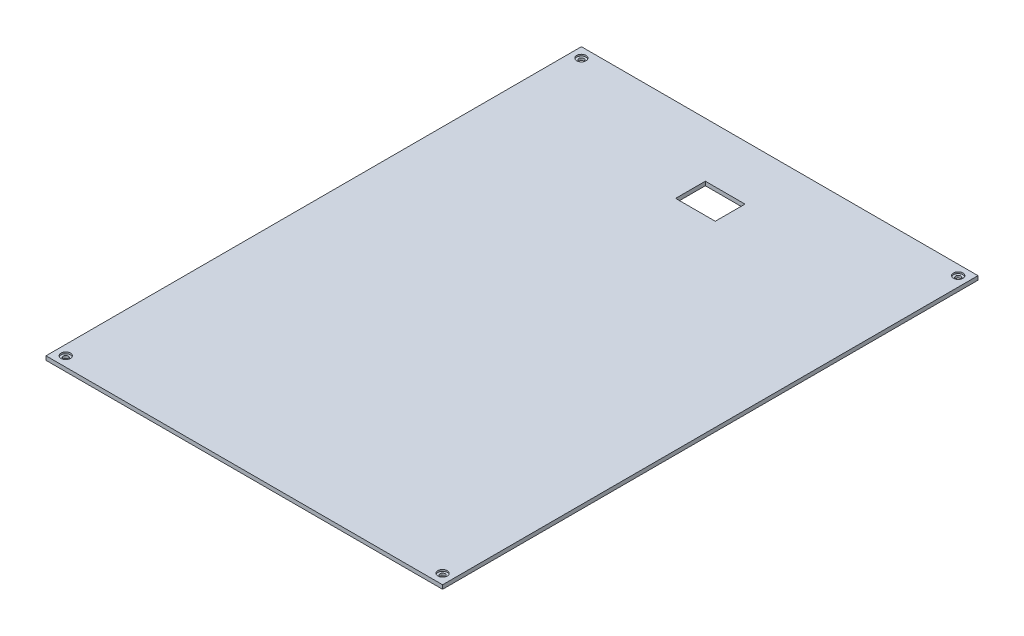
SolidWorks part; units mm, degrees
material "PLA"
ref_plane "Спереди" through (0, 0, 0) normal (0, 0, 1) x (1, 0, 0)
ref_plane "Сверху" through (0, 0, 0) normal (0, 1, 0) x (1, 0, 0)
ref_plane "Справа" through (0, 0, 0) normal (1, 0, 0) x (0, 0, -1)
sketch "Эскиз1" plane through (0, 0, 0) normal (0, 1, 0) x (1, 0, 0)
  line L1 (100, 135) -> (-100, 135)
  line L2 (100, 135) -> (100, -135)
  line L3 (100, -135) -> (-100, -135)
  line L4 (-100, 135) -> (-100, -135)
  line L5 (100, 135) -> (-100, -135) construction
  line L6 (100, -135) -> (-100, 135) construction
  point P0 (0, 0)
  dimension "D1" = 200
  dimension "D2" = 270
extrude "Бобышка-Вытянуть1" add sketch "Эскиз1" along normal blind 2
sketch "Эскиз2" plane through (0, 2, 0) normal (0, 1, 0) x (1, 0, 0)
  line L0 (0, 0) -> (0, 50000) construction
  line L1 (0, 0) -> (-50000, 0) construction
  line L2 (-100, 135) -> (-100, -135) construction
  line L3 (100, 135) -> (-100, 135) construction
  circle A0 centre (-95.0102, 130.0102) radius 1.3
  circle A1 centre (95.0102, 130.0102) radius 1.3
  circle A2 centre (95.0102, -130.0102) radius 1.3
  circle A3 centre (-95.0102, -130.0102) radius 1.3
  dimension "D1" = 2.6
  dimension "D2" = 4.9898
  dimension "D3" = 4.9898
extrude "Вырез-Вытянуть1" cut sketch "Эскиз2" against normal through all
sketch "Эскиз3" plane through (0, 2, 0) normal (0, 1, 0) x (1, 0, 0)
  circle A0 centre (-95.0102, 130.0102) radius 2.375
  circle A1 centre (95.0102, 130.0102) radius 2.375
  circle A2 centre (-95.0102, -130.0102) radius 2.375
  circle A3 centre (95.0102, -130.0102) radius 2.375
  dimension "D1" = 4.75
extrude "Вырез-Вытянуть2" cut sketch "Эскиз3" against normal blind 0.8
sketch "Эскиз4" plane through (0, 2, 0) normal (0, 1, 0) x (1, 0, 0)
  line L0 (0, 0) -> (0, 50000) construction
  line L1 (10, 107.5) -> (-10, 107.5)
  line L2 (10, 107.5) -> (10, 92.5)
  line L3 (10, 92.5) -> (-10, 92.5)
  line L4 (-10, 107.5) -> (-10, 92.5)
  line L5 (10, 107.5) -> (-10, 92.5) construction
  line L6 (10, 92.5) -> (-10, 107.5) construction
  line L7 (100, 135) -> (-100, 135) construction
  point P0 (0, 100)
  point P8 (0, 99.7252)
  dimension "D1" = 20
  dimension "D2" = 15
  dimension "D3" = 35
extrude "Вырез-Вытянуть3" cut sketch "Эскиз4" against normal through all
sketch "Эскиз5" plane through (0, 0, 0) normal (0, -1, 0) x (1, 0, 0)
  line L0 (100, -135) -> (-100, -135) construction
  line L1 (100, 135) -> (100, -135) construction
  circle A0 centre (-3.9, -120.15) radius 1.75
  circle A1 centre (6.25, -88.45) radius 1.75
  circle A2 centre (-3.9, -120.15) radius 2.75
  circle A3 centre (6.25, -88.45) radius 2.75
  dimension "D1" = 3.5
  dimension "D2" = 14.85
  dimension "D3" = 103.9
  dimension "D4" = 10.15
  dimension "D5" = 31.7
  dimension "D6" = 1
extrude "Бобышка-Вытянуть2" add sketch "Эскиз5" along normal blind 2.7
